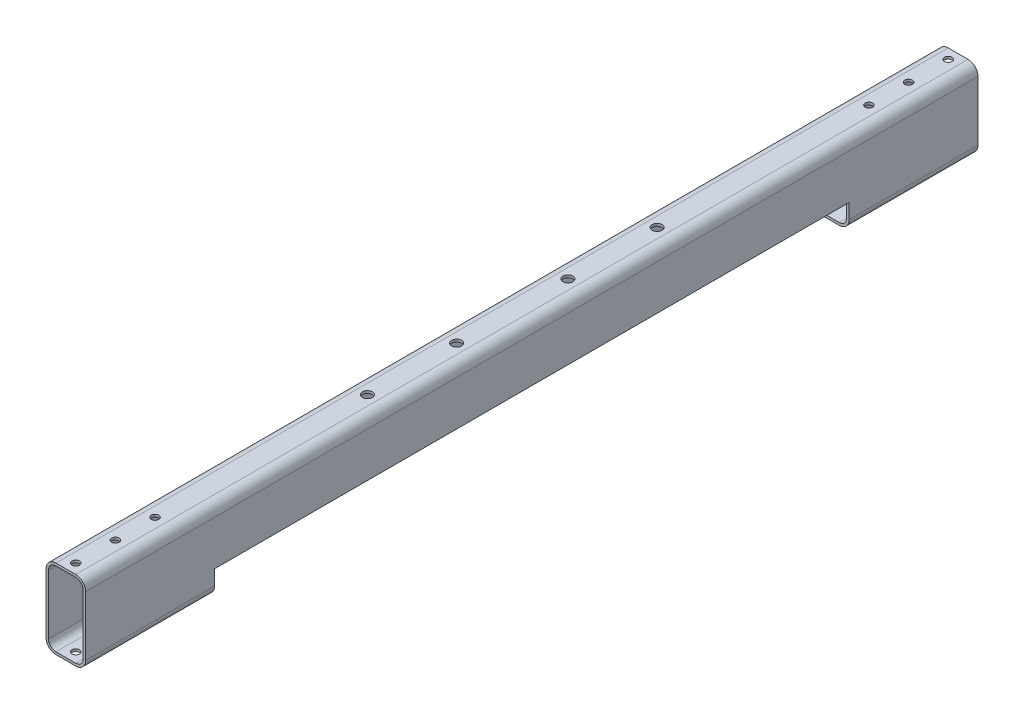
SolidWorks part; units mm, degrees
material "6061-T6 (SS)"
ref_plane "Front Plane" through (0, 0, 0) normal (0, 0, 1) x (1, 0, 0)
ref_plane "Top Plane" through (0, 0, 0) normal (0, 1, 0) x (1, 0, 0)
ref_plane "Right Plane" through (0, 0, 0) normal (1, 0, 0) x (0, 0, -1)
sketch "Sketch1" plane through (0, 0, 0) normal (0, 0, 1) x (1, 0, 0)
  line L1 (-6.35, -25.4) -> (6.35, -25.4)
  line L2 (-12.7, -19.05) -> (-12.7, 19.05)
  line L3 (-6.35, 25.4) -> (6.35, 25.4)
  line L4 (12.7, -19.05) -> (12.7, 19.05)
  line L5 (-12.7, -25.4) -> (12.7, 25.4) construction
  line L6 (-12.7, 25.4) -> (12.7, -25.4) construction
  arc A0 (-12.7, -19.05) -> (-6.35, -25.4) centre (-6.35, -19.05) ccw
  arc A1 (6.35, -25.4) -> (12.7, -19.05) centre (6.35, -19.05) ccw
  arc A2 (6.35, 25.4) -> (12.7, 19.05) centre (6.35, 19.05) cw
  arc A3 (-12.7, 19.05) -> (-6.35, 25.4) centre (-6.35, 19.05) cw
  point P0 (0, 0)
  dimension "D3" = 6.35
  dimension "D1" = 50.8
  dimension "D2" = 25.4
extrude "Extrude-Thin1" add sketch "Sketch1" along normal blind 571.5 thin thin type one direction reverse wall 1.5875
hole_wizard "3/16 (0.1875) Diameter Hole1" positions "3DSketch1" profile "Sketch3" hole size "3/16" standard "ANSI Inch" end condition through all
sketch3d "3DSketch1"
  line L1 (6.35, 25.4, 0) -> (-6.35, 25.4, 0) construction
  line L6 (0, 25.4, 571.5) -> (0, 25.4, 0) construction
  line L7 (6.35, 25.4, 571.5) -> (-6.35, 25.4, 571.5) construction
  point P57 (0, 25.4, 6.35)
  point P59 (0, 25.4, 31.75)
  point P61 (0, 25.4, 57.15)
  point P63 (0, 25.4, 539.75)
  point P65 (0, 25.4, 514.35)
  point P67 (0, 25.4, 565.15)
  dimension "D1" = 25.4
  dimension "D2" = 25.4
  dimension "D3" = 6.35
  dimension "D4" = 25.4
  dimension "D5" = 25.4
  dimension "D6" = 6.35
sketch "Sketch3" plane through (0, 25.4, 565.15) normal (1, 0, 0) x (0, 0, 1)
  line L0 (0, 0) -> (0, 50.8)
  line L1 (0, 50.8) -> (2.3812, 50.8)
  line L2 (2.3812, 50.8) -> (2.3812, 0)
  line L5 (2.3812, 0) -> (0, 0)
  line L11 (0, -6.35) -> (0, 107.95) construction
  dimension "Thru Hole Dia." = 4.7625
  dimension "Thru Hole Depth" = 50.8
sketch "Sketch5" plane through (12.7, 0, 0) normal (1, 0, 0) x (0, 0, -1)
  line L0 (-488.95, -9.525) -> (-488.95, -25.4)
  line L2 (-488.95, -25.4) -> (-82.55, -25.4)
  line L3 (-82.55, -25.4) -> (-82.55, -9.525)
  line L4 (-82.55, -9.525) -> (-488.95, -9.525)
  line L12 (-571.5, -25.4) -> (0, -25.4) construction
  point P11 (-285.75, -25.4)
  point P12 (-285.75, -25.4)
  dimension "D1" = 15.875
  dimension "D2" = 406.4
extrude "Cut-Extrude1" cut sketch "Sketch5" against normal through all
hole_wizard "1/4 (0.25) Diameter Hole1" positions "Sketch6" profile "Sketch7" hole size "1/4" standard "ANSI Inch" end condition through all
sketch "Sketch6" plane through (0, 25.4, 0) normal (0, 1, 0) x (1, 0, 0)
  point P0 (0, -321.183)
  point P3 (0, -378.333)
  point P6 (0, -192.786)
  point P9 (0, -249.936)
sketch "Sketch7" plane through (0, 25.4, 321.183) normal (1, 0, 0) x (0, 0, 1)
  line L0 (0, 0) -> (0, 50.8)
  line L1 (0, 50.8) -> (3.175, 50.8)
  line L2 (3.175, 50.8) -> (3.175, 0)
  line L5 (3.175, 0) -> (0, 0)
  line L11 (0, -6.35) -> (0, 107.95) construction
  dimension "Thru Hole Dia." = 6.35
  dimension "Thru Hole Depth" = 50.8
hole_wizard "E (0.25) Diameter Hole1" positions "Sketch8" profile "Sketch9" hole size "E" standard "ANSI Inch"
sketch "Sketch8" plane through (-12.7, 0, 0) normal (-1, 0, 0) x (0, 0, 1)
  point P0 (103.886, 17.145)
  point P3 (103.886, 1.27)
  point P6 (116.586, 8.89)
  point P13 (454.914, 8.89)
  point P16 (467.614, 1.27)
  point P19 (467.614, 17.145)
sketch "Sketch9" plane through (-12.7, 17.145, 103.886) normal (0, 1, 0) x (0, 0, 1)
  line L0 (0, 0) -> (0, 8.2577)
  line L1 (0, 8.2577) -> (3.175, 6.35)
  line L2 (3.175, 6.35) -> (3.175, 0)
  line L5 (3.175, 0) -> (0, 0)
  line L10 (0, 8.2577) -> (-3.175, 6.35) construction
  line L11 (0, -6.35) -> (0, 107.95) construction
  dimension "Hole Dia." = 6.35
  dimension "Hole Depth" = 6.35
  dimension "Drill Angle" = 118
